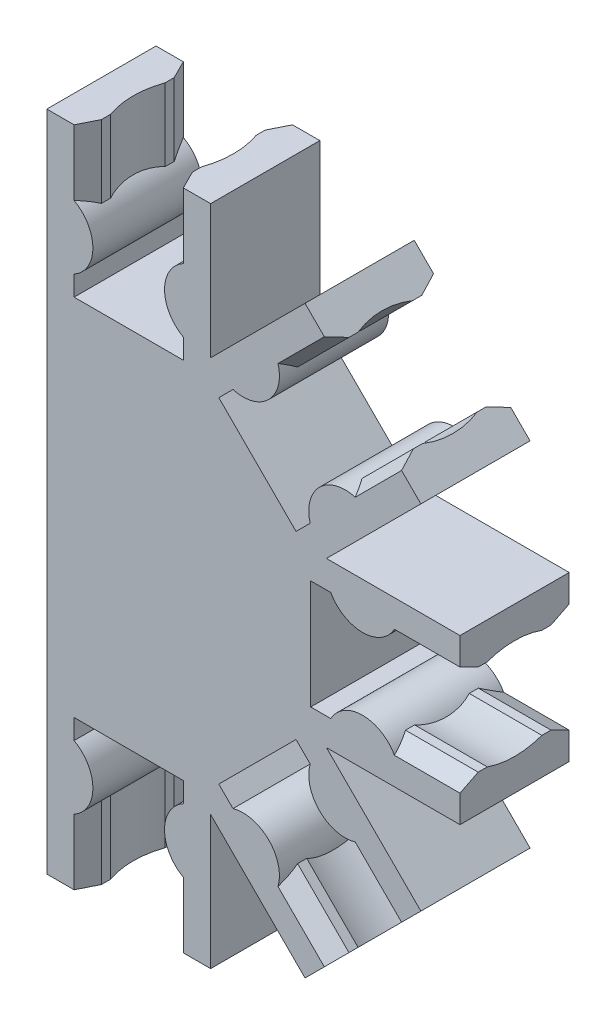
SolidWorks part; units mm, degrees
ref_plane "前视基准面" through (0, 0, 0) normal (0, 0, 1) x (1, 0, 0)
ref_plane "上视基准面" through (0, 0, 0) normal (0, 1, 0) x (1, 0, 0)
ref_plane "右视基准面" through (0, 0, 0) normal (1, 0, 0) x (0, 0, -1)
sketch "草图1" plane through (0, 0, 0) normal (0, 0, 1) x (1, 0, 0)
  line L0 (-4.5, 0) -> (-4.5, -18.2)
  line L1 (4.5, 0) -> (4.5, -18.2)
  line L2 (-4.5, -18.2) -> (-3, -18.2)
  line L3 (-3, -18.2) -> (-3, -14.6)
  line L4 (4.5, -18.2) -> (3, -18.2)
  line L5 (3, -18.2) -> (3, -14.6)
  line L6 (-3, -11.1) -> (-3, -10)
  line L7 (-3, -10) -> (3, -10)
  line L8 (3, -10) -> (3, -11.1)
  arc A0 (4.5, 0) -> (-4.5, 0) centre (0, 0) ccw
  arc A1 (-3, -11.1) -> (-3, -14.6) centre (-3.9682, -12.85) cw
  arc A2 (3, -11.1) -> (3, -14.6) centre (3.9682, -12.85) ccw
  point P1 (0, 4.5)
  dimension "D1" = 9
  dimension "D10" = 14.5
  dimension "D11" = 2
  dimension "D12" = 2
  dimension "D2" = 18.2
  dimension "D3" = 18.2
  dimension "D4" = 1.5
  dimension "D5" = 1.5
  dimension "D6" = 1.1
  dimension "D7" = 1.1
  dimension "D8" = 3.5
  dimension "D9" = 3.5
extrude "凸台-拉伸1" add sketch "草图1" along normal blind 6
sketch "草图3" plane through (0, -18.2, 0) normal (0, -1, 0) x (1, 0, 0)
  line L0 (-3, 6) -> (-3, 0)
  line L1 (-3, 0) -> (-2.5, 1)
  line L2 (-2.5, 1) -> (-2.5, 1.5)
  line L3 (-3, 6) -> (-2.5, 5)
  line L4 (-2.5, 5) -> (-2.5, 4.5)
  line L5 (0, 0) -> (0, 6.4845) construction
  line L6 (3, 0) -> (2.5, 1)
  line L7 (2.5, 1) -> (2.5, 1.5)
  line L8 (2.5, 5) -> (2.5, 4.5)
  line L9 (3, 6) -> (2.5, 5)
  line L10 (3, 6) -> (3, 0)
  arc A0 (-2.5, 1.5) -> (-2.5, 4.5) centre (1.7426, 3) cw
  arc A1 (2.5, 1.5) -> (2.5, 4.5) centre (-1.7426, 3) ccw
  dimension "D7" = 4.5
  dimension "D1" = 0.5
  dimension "D2" = 0.5
  dimension "D3" = 0.5
  dimension "D4" = 0.5
  dimension "D5" = 1.5
  dimension "D6" = 1.5
extrude "凸台-拉伸2" add sketch "草图3" against normal up to next
ref_axis "Axis" through (0, 0, 0) along (0, 0, 1)
pattern_circular "阵列(圆周)1" count 5 every 45 about axis through (0, 0, 0) along (0, 0, 1) of "凸台-拉伸1", "凸台-拉伸2"
sketch "草图4" plane through (0, 0, 0) normal (0, 0, -1) x (-1, 0, 0)
  line L0 (3, -8.75) -> (3, -3.3541)
  line L1 (3, -8.75) -> (-3, -8.75)
  line L2 (-3, -8.75) -> (-1.1749, -4.3439)
  line L3 (0, 0) -> (-4.5, -10.864) construction
  line L4 (3, -10) -> (-3, -10) construction
  line L5 (0, 0) -> (-10.864, -4.5) construction
  line L6 (-4.0659, -8.3085) -> (-8.3085, -4.0659)
  line L7 (-4.9497, -9.1924) -> (-9.1924, -4.9497) construction
  line L8 (0, 0) -> (-7.0711, -7.0711) construction
  line L9 (-8.3085, -4.0659) -> (-3.9024, -2.2408)
  line L10 (-4.0659, -8.3085) -> (-2.2408, -3.9024)
  line L11 (0, 0) -> (-10, 0) construction
  line L12 (-10, -3) -> (-10, 3) construction
  line L13 (3, 8.75) -> (3, 3.3541)
  line L14 (3, 8.75) -> (-3, 8.75)
  line L15 (-3, 8.75) -> (-1.1749, 4.3439)
  line L16 (-8.75, 3) -> (-4.3439, 1.1749)
  line L17 (-8.75, -3) -> (-8.75, 3)
  line L18 (-8.75, -3) -> (-4.3439, -1.1749)
  line L19 (-4.0659, 8.3085) -> (-2.2408, 3.9024)
  line L20 (-8.3085, 4.0659) -> (-4.0659, 8.3085)
  line L21 (-8.3085, 4.0659) -> (-3.9024, 2.2408)
  circle A0 centre (0, 0) radius 3
  arc A1 (-2.2408, 3.9024) -> (-3.9024, 2.2408) centre (0, 0) ccw
  arc A2 (-4.3439, 1.1749) -> (-4.3439, -1.1749) centre (0, 0) ccw
  arc A3 (-3.9024, -2.2408) -> (-2.2408, -3.9024) centre (0, 0) ccw
  arc A4 (-1.1749, -4.3439) -> (3, -3.3541) centre (0, 0) ccw
  arc A5 (3, 3.3541) -> (-1.1749, 4.3439) centre (0, 0) ccw
  point P5 (-6.1872, -6.1872)
  point P41 (0, 0)
  dimension "D1" = 6
  dimension "D2" = 9
  dimension "D3" = 6
  dimension "D4" = 1.25
  dimension "D5" = 6
  dimension "D6" = 1.25
  dimension "D7" = 3
